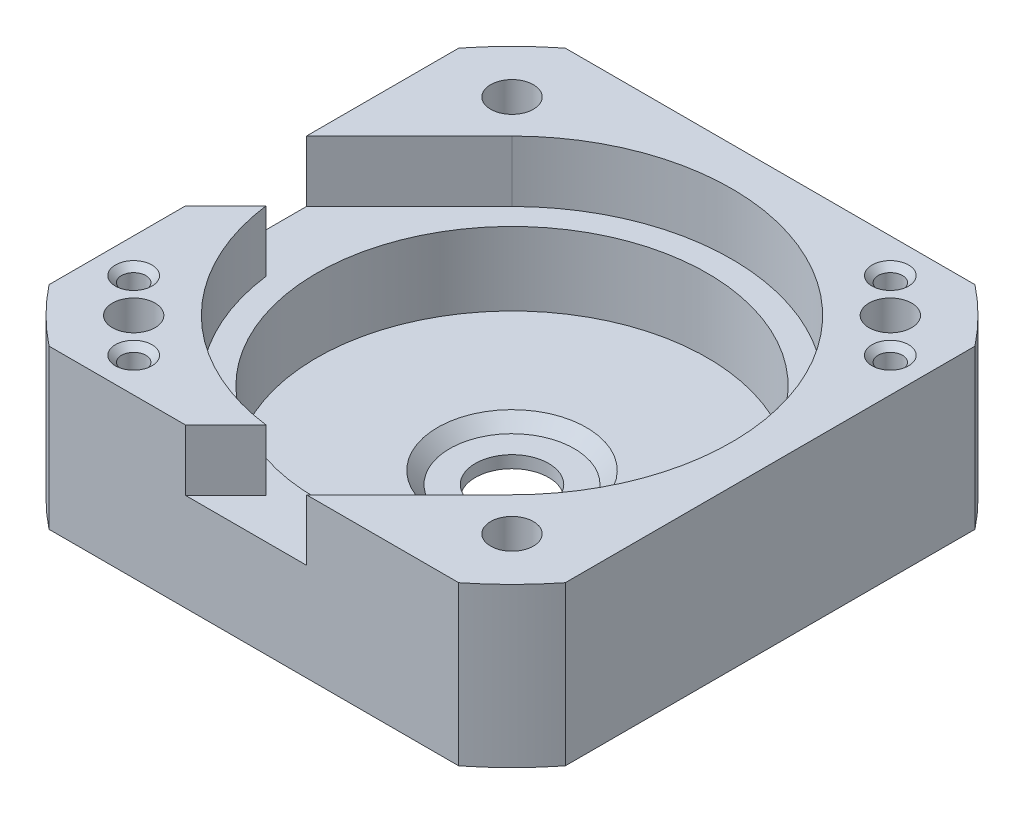
SolidWorks part; units mm, degrees
ref_plane "Front Plane" through (0, 0, 0) normal (0, 0, 1) x (1, 0, 0)
ref_plane "Top Plane" through (0, 0, 0) normal (0, 1, 0) x (1, 0, 0)
ref_plane "Right Plane" through (0, 0, 0) normal (1, 0, 0) x (0, 0, -1)
sketch "Sketch2" plane through (0, 0, 0) normal (0, 1, 0) x (1, 0, 0)
  line L1 (-21.15, 21.15) -> (21.15, 21.15)
  line L2 (-21.15, 21.15) -> (-21.15, -21.15)
  line L3 (-21.15, -21.15) -> (21.15, -21.15)
  line L4 (21.15, 21.15) -> (21.15, -21.15)
  line L5 (-21.15, 21.15) -> (21.15, -21.15) construction
  line L6 (-21.15, -21.15) -> (21.15, 21.15) construction
  point P0 (0, 0)
  dimension "D1" = 42.3
extrude "Boss-Extrude1" add sketch "Sketch2" along normal blind 13
sketch "Sketch3" plane through (0, 13, 0) normal (0, 1, 0) x (1, 0, 0)
  circle A0 centre (0, 0) radius 3
  dimension "D1" = 6
extrude "Cut-Extrude1" cut sketch "Sketch3" against normal through all
sketch "Sketch4" plane through (0, 13, 0) normal (0, 1, 0) x (1, 0, 0)
  line L1 (-15.5, 15.5) -> (15.5, 15.5) construction
  line L2 (-15.5, 15.5) -> (-15.5, -15.5) construction
  line L3 (-15.5, -15.5) -> (15.5, -15.5) construction
  line L4 (15.5, 15.5) -> (15.5, -15.5) construction
  line L5 (-15.5, 15.5) -> (15.5, -15.5) construction
  line L6 (-15.5, -15.5) -> (15.5, 15.5) construction
  circle A0 centre (-15.5, 15.5) radius 1.75
  circle A1 centre (15.5, 15.5) radius 1.75
  circle A2 centre (15.5, -15.5) radius 1.75
  circle A3 centre (-15.5, -15.5) radius 1.75
  point P0 (0, 0)
  point P16 (0, 0)
  dimension "D3" = 3.5
  dimension "D1" = 31
  dimension "D2" = 31
  dimension "D4" = 4
extrude "Cut-Extrude2" cut sketch "Sketch4" against normal through all
sketch "Sketch5" plane through (0, 13, 0) normal (0, 1, 0) x (1, 0, 0)
  circle A0 centre (0, 0) radius 27
  circle A1 centre (0, 0) radius 29.9106
  dimension "D1" = 54
extrude "Cut-Extrude4" cut sketch "Sketch5" against normal through all
sketch "Sketch6" plane through (0, 13, 0) normal (0, 1, 0) x (1, 0, 0)
  line L0 (-21.15, 4.3058) -> (-12.7279, 12.7279)
  line L1 (12.7279, -12.7279) -> (4.3058, -21.15)
  line L9 (-21.15, 16.7833) -> (-21.15, -16.7833) construction
  line L10 (-16.7833, -21.15) -> (16.7833, -21.15) construction
  line L11 (-7.7782, 7.7782) -> (-21.15, -5.5937) construction
  line L12 (4.3058, 21.15) -> (21.15, 4.3058) construction
  line L13 (7.3751, 21.15) -> (21.15, 7.3751) construction
  line L14 (16.7833, 21.15) -> (-16.7833, 21.15) construction
  line L15 (21.15, -16.7833) -> (21.15, 16.7833) construction
  line L18 (7.7782, -7.7782) -> (-5.5937, -21.15) construction
  line L19 (-21.15, 4.3058) -> (-21.15, -5.5937)
  line L21 (-2.2965, -17.8529) -> (-5.5937, -21.15)
  line L22 (-5.5937, -21.15) -> (4.3058, -21.15)
  line L23 (-17.8529, -2.2965) -> (-21.15, -5.5937)
  arc A0 (-12.7279, 12.7279) -> (12.7279, -12.7279) centre (0, 0) cw
  arc A2 (-17.8529, -2.2965) -> (-2.2965, -17.8529) centre (0, 0) ccw
  circle A3 centre (0, 0) radius 11 construction
  circle A5 centre (15.5, 15.5) radius 1.75 construction
  arc A6 (12.7279, -12.7279) -> (-12.7279, 12.7279) centre (0, 0) ccw
  circle M13 centre (0, 0) radius 3
  line M14 (-16.7833, -21.15) -> (16.7833, -21.15)
  line M20 (-21.15, 16.7833) -> (-21.15, -16.7833)
  dimension "D1" = 45
  dimension "D3" = 18
  dimension "D5" = 22
  dimension "D2" = 45
  dimension "D4" = 45
extrude "Cut-Extrude5" cut sketch "Sketch6" against normal offset from surface (11 mm away) 2 contours L23 A2 L21 L1 A0 L0 M14 M20 M13 region at (-16.5475, 13, -8.1254) up to face at (-15.5, 0, 17.25)
chamfer "Chamfer1" distance 1.8 angle 45 4 edges at (15.5, 0, -13.75) (-15.5, 0, -13.75) (-15.5, 0, 17.25) (15.5, 0, 17.25)
sketch "Sketch7" plane through (0, 2, 0) normal (0, 1, 0) x (1, 0, 0)
  circle A0 centre (0, 0) radius 5.1
  dimension "D1" = 10.2
extrude "Cut-Extrude6" cut sketch "Sketch7" against normal blind 1
sketch "Sketch8" plane through (0, 2, 0) normal (0, 1, 0) x (1, 0, 0)
  line L6 (-21.15, 4.3058) -> (-21.15, -5.5937)
  line L7 (-21.15, -5.5937) -> (-17.8529, -2.2965)
  line L8 (-2.2965, -17.8529) -> (-5.5937, -21.15)
  line L9 (-5.5937, -21.15) -> (4.3058, -21.15)
  line L10 (4.3058, -21.15) -> (12.7279, -12.7279)
  line L11 (-12.7279, 12.7279) -> (-21.15, 4.3058)
  line L12 (-21.15, 4.3058) -> (-21.15, -5.5937)
  line L13 (-21.15, -5.5937) -> (-17.8529, -2.2965)
  line L14 (-2.2965, -17.8529) -> (-5.5937, -21.15)
  line L15 (-5.5937, -21.15) -> (4.3058, -21.15)
  line L16 (4.3058, -21.15) -> (12.7279, -12.7279)
  line L17 (-12.7279, 12.7279) -> (-21.15, 4.3058)
  circle A0 centre (0, 0) radius 16
  arc A3 (-17.8529, -2.2965) -> (-2.2965, -17.8529) centre (0, 0) ccw
  arc A4 (12.7279, -12.7279) -> (-12.7279, 12.7279) centre (0, 0) ccw
  arc A5 (-17.8529, -2.2965) -> (-2.2965, -17.8529) centre (0, 0) ccw
  arc A6 (12.7279, -12.7279) -> (-12.7279, 12.7279) centre (0, 0) ccw
  dimension "D1" = 32
  dimension "D2" = 0
extrude "Boss-Extrude2" add sketch "Sketch8" along normal offset from surface (6 mm away) 5 up to face at (-15.5, 13, -13.75)
chamfer "Chamfer2" distance 1 angle 45 1 edges at (0, 2, 5.1)
sketch "Sketch9" plane through (0, 13, 0) normal (0, 1, 0) x (1, 0, 0)
  line L0 (12.6716, 18.3284) -> (18.3284, 12.6716) construction
  line L1 (4.3058, -21.15) -> (16.7833, -21.15) construction
  line L2 (-19.0919, 19.0919) -> (19.0919, -19.0919) construction
  line L3 (-18.3284, -12.6716) -> (-12.6716, -18.3284) construction
  circle A0 centre (15.5, 15.5) radius 1.75 construction
  circle A1 centre (12.6716, 18.3284) radius 1
  circle A2 centre (18.3284, 12.6716) radius 1
  arc A3 (-16.7833, 21.15) -> (-21.15, 16.7833) centre (0, 0) ccw construction
  arc A4 (16.7833, -21.15) -> (21.15, -16.7833) centre (0, 0) ccw construction
  circle A5 centre (-12.6716, -18.3284) radius 1
  circle A6 centre (-18.3284, -12.6716) radius 1
  point P2 (15.5, 15.5)
  dimension "D2" = 2
  dimension "D3" = 2
  dimension "D1" = 4
  dimension "D4" = 45
extrude "Cut-Extrude7" cut sketch "Sketch9" against normal blind 3
chamfer "Chamfer3" distance 0.5 angle 45 4 edges at (12.6716, 13, -17.3284) (18.3284, 13, -11.6716) (-12.6716, 13, 17.3284) (-18.3284, 13, 11.6716)
